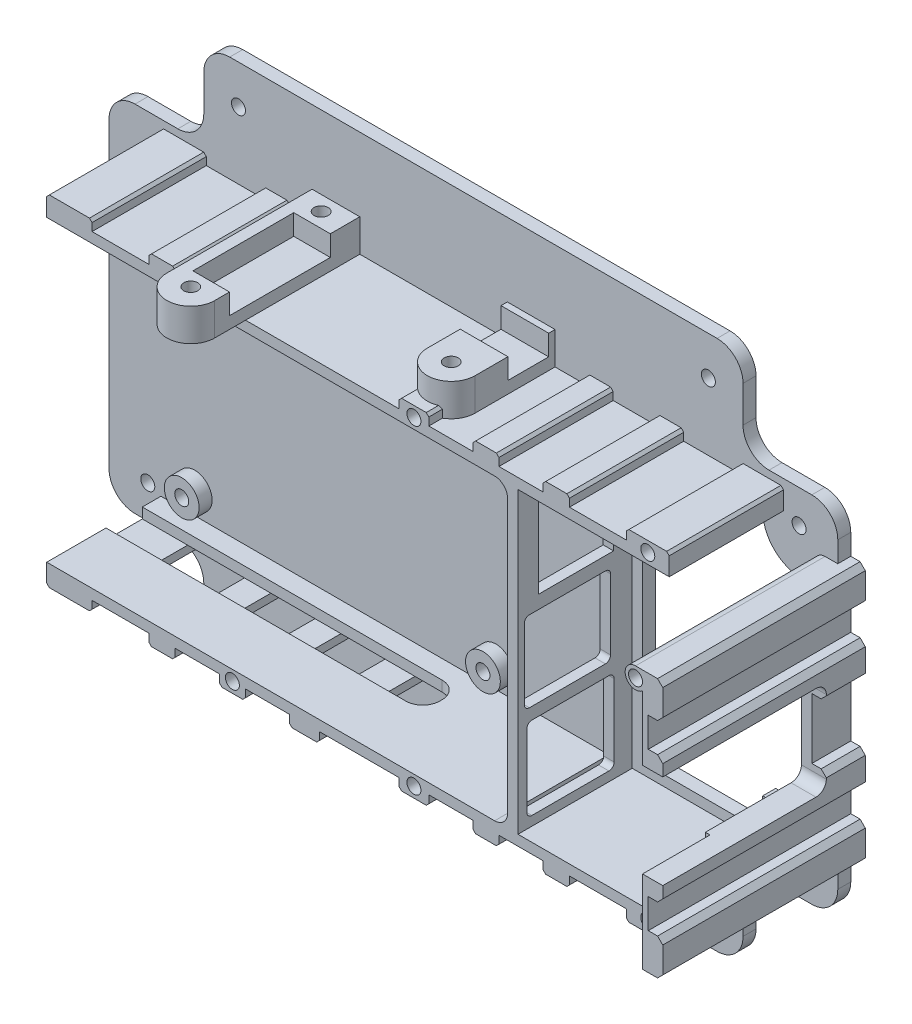
SolidWorks part; units mm, degrees
ref_plane "Front Plane" through (0, 0, 0) normal (0, 0, 1) x (1, 0, 0)
ref_plane "Top Plane" through (0, 0, 0) normal (0, 1, 0) x (1, 0, 0)
ref_plane "Right Plane" through (0, 0, 0) normal (1, 0, 0) x (0, 0, -1)
sketch "Sketch1" plane through (0, 0, 0) normal (0, 0, 1) x (1, 0, 0)
  line L0 (-70.167, -29.1473) -> (-70.167, 29.1473)
  line L1 (-65.167, 34.1473) -> (-56.9198, 34.1473)
  line L2 (-51.9198, 39.1473) -> (-51.9198, 46.117)
  line L3 (-46.9198, 51.117) -> (46.9198, 51.117)
  line L4 (51.9198, 46.117) -> (51.9198, 39.1473)
  line L5 (56.9198, 34.1473) -> (65.167, 34.1473)
  line L6 (70.167, 29.1473) -> (70.167, -29.1473)
  line L7 (65.167, -34.1473) -> (56.9198, -34.1473)
  line L8 (51.9198, -39.1473) -> (51.9198, -46.117)
  line L9 (46.9198, -51.117) -> (-46.9198, -51.117)
  line L10 (-51.9198, -46.117) -> (-51.9198, -39.1473)
  line L11 (-56.9198, -34.1473) -> (-65.167, -34.1473)
  line L12 (44.45, 53.117) -> (-44.45, 53.117) construction
  line L13 (-53.9198, 51.6209) -> (-53.9198, 45.3238) construction
  line L14 (-63.0963, 36.1473) -> (-70.6694, 36.1473) construction
  line L15 (-72.167, 28.575) -> (-72.167, -28.575) construction
  line L16 (-70.6694, -36.1473) -> (-63.0963, -36.1473) construction
  line L18 (-44.45, -53.117) -> (44.45, -53.117) construction
  line L19 (53.9198, 45.3238) -> (53.9198, 51.6209) construction
  line L21 (72.167, -28.575) -> (72.167, 28.575) construction
  circle A1 centre (-62.7062, -27.7812) radius 1.35
  circle A3 centre (-45.2437, -43.6562) radius 1.35
  circle A4 centre (45.2438, -43.6562) radius 1.35
  circle A5 centre (62.7063, -27.7812) radius 1.35
  circle A6 centre (62.7063, 27.7812) radius 1.35
  circle A7 centre (45.2438, 43.6562) radius 1.35
  circle A8 centre (-45.2437, 43.6562) radius 1.35
  circle A9 centre (-62.7062, 27.7812) radius 1.35
  arc A11 (-51.9198, 46.117) -> (-46.9198, 51.117) centre (-46.9198, 46.117) cw
  arc A12 (46.9198, 51.117) -> (51.9198, 46.117) centre (46.9198, 46.117) cw
  arc A13 (65.167, 34.1473) -> (70.167, 29.1473) centre (65.167, 29.1473) cw
  arc A14 (70.167, -29.1473) -> (65.167, -34.1473) centre (65.167, -29.1473) cw
  arc A15 (-46.9198, -51.117) -> (-51.9198, -46.117) centre (-46.9198, -46.117) cw
  arc A16 (46.9198, -51.117) -> (51.9198, -46.117) centre (46.9198, -46.117) ccw
  arc A17 (-65.167, 34.1473) -> (-70.167, 29.1473) centre (-65.167, 29.1473) ccw
  arc A18 (-70.167, -29.1473) -> (-65.167, -34.1473) centre (-65.167, -29.1473) ccw
  arc A19 (-56.9198, -34.1473) -> (-51.9198, -39.1473) centre (-56.9198, -39.1473) cw
  arc A20 (51.9198, -39.1473) -> (56.9198, -34.1473) centre (56.9198, -39.1473) cw
  arc A21 (51.9198, 39.1473) -> (56.9198, 34.1473) centre (56.9198, 39.1473) ccw
  arc A22 (-51.9198, 39.1473) -> (-56.9198, 34.1473) centre (-56.9198, 39.1473) cw
  point P49 (53.9198, 48.4724)
  dimension "D1" = 2.7
  dimension "D10" = 5
  dimension "D11" = 2.7
  dimension "D12" = 2.7
  dimension "D13" = 2.7
  dimension "D14" = 2.7
  dimension "D15" = 2.7
  dimension "D16" = 2.7
  dimension "D17" = 2.7
  dimension "D2" = 2
  dimension "D3" = 2
  dimension "D4" = 2
  dimension "D5" = 2
  dimension "D6" = 2
  dimension "D7" = 2
  dimension "D8" = 2
  dimension "D9" = 2
extrude "Boss-Extrude1" add sketch "Sketch1" along normal blind 2.5
sketch "Sketch3" plane through (0, 0, 2.5) normal (0, 0, 1) x (1, 0, 0)
  line L0 (-53.667, 24.5) -> (-53.667, 34.1473) construction
  line L1 (-70.167, 29.1473) -> (-70.167, -29.1473) construction
  line L2 (-56.9198, 34.1473) -> (-65.167, 34.1473) construction
  line L3 (-53.667, -24.5) -> (-53.667, -34.1473) construction
  line L4 (-65.167, -34.1473) -> (-56.9198, -34.1473) construction
  circle A0 centre (4.333, -24.5) radius 1.35
  circle A1 centre (4.333, 24.5) radius 1.35
  circle A2 centre (-53.667, 24.5) radius 1.35
  circle A3 centre (-53.667, -24.5) radius 1.35
  circle A4 centre (-53.667, 24.5) radius 3.35
  circle A5 centre (-53.667, -24.5) radius 3.35
  circle A6 centre (4.333, -24.5) radius 3.35
  circle A7 centre (4.333, 24.5) radius 3.35
  dimension "D4" = 2.7
  dimension "D5" = 16.5
  dimension "D1" = 49
  dimension "D2" = 58
  dimension "D3" = 2
extrude "Boss-Extrude3" add sketch "Sketch3" along normal blind 2.5
sketch "Sketch4" plane through (0, 0, 2.5) normal (0, 0, 1) x (1, 0, 0)
  circle A0 centre (-53.667, 24.5) radius 1.35
  circle A1 centre (4.333, 24.5) radius 1.35
  circle A2 centre (-53.667, -24.5) radius 1.35
  circle A3 centre (4.333, -24.5) radius 1.35
extrude "Cut-Extrude1" cut sketch "Sketch4" against normal up to surface (2.5 mm away) up to face at (-43.8937, 43.6562, 0)
sketch "Sketch5" plane through (0, 0, 2.5) normal (0, 0, 1) x (1, 0, 0)
  line L0 (24.833, 28) -> (-54.167, 28) construction
  line L1 (-60.167, 28.75) -> (26.083, 28.75)
  line L3 (-60.167, -28.75) -> (26.083, -28.75)
  line L4 (28.583, 26.25) -> (28.583, -26.25)
  line L5 (27.833, -25) -> (27.833, 25) construction
  line L7 (-54.167, -28) -> (24.833, -28) construction
  line L12 (-60.167, 30.75) -> (28.083, 30.75)
  line L14 (-60.167, -30.75) -> (28.083, -30.75)
  line L17 (30.583, 30.75) -> (30.583, -30.75) construction
  line L18 (-62.167, 30.75) -> (-62.167, -30.75) construction
  line L19 (-60.167, 28.75) -> (-60.167, -28.75) construction
  line L20 (-62.167, -30.75) -> (30.583, -30.75) construction
  line L21 (-60.167, -28.75) -> (28.583, -28.75) construction
  line L22 (28.583, 28.75) -> (28.583, -28.75) construction
  line L23 (-62.167, 30.75) -> (30.583, 30.75) construction
  line L24 (-60.167, 28.75) -> (28.583, 28.75) construction
  line L25 (30.583, -28.75) -> (57.7063, -28.75)
  line L27 (59.7063, -30.75) -> (28.083, -30.75)
  line L28 (28.083, 30.75) -> (59.7063, 30.75)
  line L29 (59.7063, 30.75) -> (59.7063, 28.75)
  line L30 (59.7063, 28.75) -> (30.583, 28.75)
  line L31 (-60.167, -28.75) -> (-60.167, -30.75)
  line L32 (-60.167, 28.75) -> (-60.167, 30.75)
  line L33 (30.583, 28.75) -> (30.583, -28.75)
  line L34 (-70.167, 29.1473) -> (-70.167, -29.1473) construction
  line L35 (59.7063, -24.7812) -> (59.7063, -30.75)
  line L36 (59.7063, -25.7) -> (59.7063, 20.73) construction
  line L37 (57.7063, -28.75) -> (57.7063, -22.7813)
  line L38 (67.717, 21.5375) -> (67.717, -23.3459) construction
  line L40 (68.167, 21.2013) -> (68.167, -22.7813)
  line L41 (67.717, 12.679) -> (68.167, 12.679) construction
  line L42 (67.717, 12.679) -> (68.167, 12.679) construction
  line L43 (57.7063, -22.7813) -> (68.167, -22.7813)
  line L45 (59.7063, -24.7812) -> (70.167, -24.7813)
  line L46 (70.167, -29.1473) -> (70.167, 29.1473) construction
  line L47 (70.167, -24.7813) -> (70.167, 25.15)
  line L48 (70.167, 25.15) -> (67.717, 25.15)
  arc A1 (26.083, -28.75) -> (28.583, -26.25) centre (26.083, -26.25) ccw
  arc A3 (26.083, 28.75) -> (28.583, 26.25) centre (26.083, 26.25) cw
  circle A4 centre (62.7063, 27.7812) radius 1.35 construction
  arc A5 (67.717, 25.15) -> (68.167, 21.2013) centre (67.717, 23.15) ccw
  dimension "D5" = 10
  dimension "D7" = 2
  dimension "D1" = 2
  dimension "D2" = 0.75
  dimension "D3" = 0.75
  dimension "D4" = 0.75
  dimension "D6" = 3
  dimension "D8" = 2
extrude "Boss-Extrude4" add sketch "Sketch5" along normal blind 22
sketch "Sketch6" plane through (30.583, 0, 0) normal (1, 0, 0) x (0, 0, -1)
  line L0 (-15.99, -26.45) -> (-13.59, -26.45) construction
  line L1 (-6.99, -11.05) -> (-21.81, -11.05)
  line L2 (-5.99, -12.05) -> (-5.99, -25.95)
  line L3 (-6.99, -26.95) -> (-21.81, -26.95)
  line L4 (-22.81, -12.05) -> (-22.81, -25.95)
  line L5 (-15.99, -11.55) -> (-13.59, -11.55) construction
  line L6 (-6.49, -12.65) -> (-6.49, -13.45) construction
  line L7 (-22.31, -16.25) -> (-22.31, -18.95) construction
  line L8 (-20.93, -8.25) -> (-17.53, -8.25) construction
  line L9 (-22.29, -8.75) -> (-7.67, -8.75)
  line L10 (-23.29, -7.75) -> (-23.29, 5.75)
  line L11 (-22.29, 6.75) -> (-7.67, 6.75)
  line L12 (-6.67, -7.75) -> (-6.67, 5.75)
  line L13 (-20.59, 9.3) -> (-6.09, 9.3)
  line L14 (-20.59, 9.3) -> (-20.59, 26.2)
  line L15 (-20.59, 26.2) -> (-6.09, 26.2)
  line L16 (-6.09, 9.3) -> (-6.09, 26.2)
  line L17 (-7.17, -6.25) -> (-7.17, -1.01) construction
  line L18 (-17.53, 6.25) -> (-20.93, 6.25) construction
  line L19 (-22.79, 4.25) -> (-22.79, -6.25) construction
  line L20 (-6.79, 9.8) -> (-19.89, 9.8) construction
  line L21 (-19.89, 25.7) -> (-6.79, 25.7) construction
  line L22 (-20.09, 10) -> (-20.09, 25.5) construction
  line L23 (-6.59, 20.18) -> (-6.59, 15.12) construction
  arc A0 (-21.81, -11.05) -> (-22.81, -12.05) centre (-21.81, -12.05) ccw
  arc A1 (-21.81, -26.95) -> (-22.81, -25.95) centre (-21.81, -25.95) cw
  arc A2 (-5.99, -25.95) -> (-6.99, -26.95) centre (-6.99, -25.95) cw
  arc A3 (-6.99, -11.05) -> (-5.99, -12.05) centre (-6.99, -12.05) cw
  arc A4 (-7.67, -8.75) -> (-6.67, -7.75) centre (-7.67, -7.75) ccw
  arc A5 (-7.67, 6.75) -> (-6.67, 5.75) centre (-7.67, 5.75) cw
  arc A6 (-23.29, 5.75) -> (-22.29, 6.75) centre (-22.29, 5.75) cw
  arc A7 (-22.29, -8.75) -> (-23.29, -7.75) centre (-22.29, -7.75) cw
  point P10 (-6.49, -13.05)
  point P35 (-19.23, 6.25)
  dimension "D5" = 1
  dimension "D10" = 1
  dimension "D1" = 0.5
  dimension "D2" = 0.5
  dimension "D3" = 0.5
  dimension "D4" = 0.5
  dimension "D6" = 0.5
  dimension "D7" = 0.5
  dimension "D8" = 0.5
  dimension "D9" = 0.5
  dimension "D11" = 0.5
  dimension "D12" = 0.5
  dimension "D13" = 0.5
  dimension "D14" = 0.5
extrude "Cut-Extrude2" cut sketch "Sketch6" against normal up to surface (2 mm away) up to face at (28.583, 0, 13.5)
sketch "Sketch8" plane through (0, -30.75, 0) normal (0, -1, 0) x (1, 0, 0)
  line L0 (-54.167, 6.59) -> (24.833, 6.59) construction
  line L1 (-60.167, 13.09) -> (-2.417, 13.09)
  line L2 (-60.167, 13.09) -> (-60.167, 6.09)
  line L3 (-60.167, 6.09) -> (-2.417, 6.09)
  line L4 (0.833, 9.84) -> (0.833, 9.34)
  line L5 (-3.167, 12.59) -> (-6.667, 12.59) construction
  line L6 (0.333, 6.59) -> (0.333, 12.59) construction
  line L9 (-60.167, 24.5) -> (-60.167, 2.5) construction
  arc A0 (-2.417, 13.09) -> (0.833, 9.84) centre (-2.417, 9.84) cw
  arc A1 (-2.417, 6.09) -> (0.833, 9.34) centre (-2.417, 9.34) ccw
  dimension "D4" = 3.25
  dimension "D1" = 0.5
  dimension "D2" = 0.5
  dimension "D3" = 0.5
extrude "Cut-Extrude3" cut sketch "Sketch8" against normal up to surface (2 mm away) up to face at (-17.042, -28.75, 13.5)
sketch "Sketch9" plane through (0, 0, 2.5) normal (0, 0, 1) x (1, 0, 0)
  line L0 (-60.167, -30.75) -> (59.7063, -30.75) construction
  line L1 (-40.497, -30.75) -> (-35.417, -30.75)
  line L2 (-40.497, -30.75) -> (-40.497, -32.25)
  line L3 (-39.997, -32.75) -> (-35.917, -32.75)
  line L4 (-35.417, -30.75) -> (-35.417, -32.25)
  line L5 (-41.497, -29.5) -> (-41.497, -21.89) construction
  line L6 (-26.917, -30.75) -> (-21.917, -30.75)
  line L7 (-26.917, -30.75) -> (-26.917, -32.25)
  line L8 (-26.417, -32.75) -> (-22.417, -32.75)
  line L9 (-21.917, -30.75) -> (-21.917, -32.25)
  line L10 (-13.417, -30.75) -> (-7.667, -30.75)
  line L11 (-13.417, -30.75) -> (-13.417, -32.25)
  line L12 (-12.917, -32.75) -> (-8.167, -32.75)
  line L13 (-7.667, -30.75) -> (-7.667, -32.25)
  line L14 (-27.917, -29.8) -> (-27.917, -22.3) construction
  line L15 (-20.917, -22.3) -> (-20.917, -29.8) construction
  line L16 (-14.417, -29.8) -> (-14.417, -22.3) construction
  line L17 (-6.667, -15.4) -> (-6.667, -23.8) construction
  line L18 (-34.417, -22.3) -> (-34.417, -29.8) construction
  line L19 (-50.437, -21.89) -> (-50.437, -29.5) construction
  line L20 (-51.437, -30.75) -> (-60.1639, -30.75)
  line L21 (-51.437, -30.75) -> (-51.437, -32.25)
  line L22 (-51.937, -32.75) -> (-59.6639, -32.75)
  line L23 (-60.1639, -30.75) -> (-60.1639, -32.25)
  line L24 (-59.6639, -32.75) -> (-60.1639, -32.25)
  line L25 (-51.437, -32.25) -> (-51.937, -32.75)
  line L26 (-35.917, -32.75) -> (-35.417, -32.25)
  line L27 (-40.497, -32.25) -> (-39.997, -32.75)
  line L28 (-26.917, -32.25) -> (-26.417, -32.75)
  line L29 (-22.417, -32.75) -> (-21.917, -32.25)
  line L30 (-8.167, -32.75) -> (-7.667, -32.25)
  line L31 (-13.417, -32.25) -> (-12.917, -32.75)
  line L32 (-70.167, 0) -> (70.167, 0) construction
  line L33 (-70.167, 29.1473) -> (-70.167, -29.1473) construction
  line L44 (-26.417, 32.75) -> (-22.417, 32.75)
  line L45 (-22.417, 32.75) -> (-21.917, 32.25)
  line L46 (-21.917, 30.75) -> (-21.917, 32.25)
  line L47 (-26.917, 30.75) -> (-21.917, 30.75)
  line L48 (-26.917, 32.25) -> (-26.417, 32.75)
  line L49 (-26.917, 30.75) -> (-26.917, 32.25)
  line L50 (-39.997, 32.75) -> (-35.917, 32.75)
  line L51 (-35.917, 32.75) -> (-35.417, 32.25)
  line L52 (-35.417, 30.75) -> (-35.417, 32.25)
  line L53 (-40.497, 30.75) -> (-35.417, 30.75)
  line L54 (-40.497, 32.25) -> (-39.997, 32.75)
  line L55 (-40.497, 30.75) -> (-40.497, 32.25)
  line L56 (-51.937, 32.75) -> (-59.6639, 32.75)
  line L57 (-59.6639, 32.75) -> (-60.1639, 32.25)
  line L58 (-60.1639, 30.75) -> (-60.1639, 32.25)
  line L59 (-51.437, 30.75) -> (-60.1639, 30.75)
  line L60 (-51.437, 32.25) -> (-51.937, 32.75)
  line L61 (-51.437, 30.75) -> (-51.437, 32.25)
  line L62 (51.437, 32.25) -> (51.937, 32.75)
  line L63 (51.437, 30.75) -> (51.437, 32.25)
  line L64 (51.437, 30.75) -> (59.7063, 30.75)
  line L65 (59.7063, 30.75) -> (59.7063, 32.25)
  line L66 (59.2063, 32.75) -> (59.7063, 32.25)
  line L67 (51.937, 32.75) -> (59.2063, 32.75)
  line L68 (40.497, 32.25) -> (39.997, 32.75)
  line L69 (40.497, 30.75) -> (40.497, 32.25)
  line L70 (40.497, 30.75) -> (35.417, 30.75)
  line L71 (35.417, 30.75) -> (35.417, 32.25)
  line L72 (35.917, 32.75) -> (35.417, 32.25)
  line L73 (39.997, 32.75) -> (35.917, 32.75)
  line L74 (26.917, 32.25) -> (26.417, 32.75)
  line L75 (26.917, 30.75) -> (26.917, 32.25)
  line L76 (26.917, 30.75) -> (21.917, 30.75)
  line L77 (21.917, 30.75) -> (21.917, 32.25)
  line L78 (22.417, 32.75) -> (21.917, 32.25)
  line L79 (26.417, 32.75) -> (22.417, 32.75)
  line L80 (13.417, 32.25) -> (12.917, 32.75)
  line L81 (13.417, 30.75) -> (13.417, 32.25)
  line L82 (13.417, 30.75) -> (7.667, 30.75)
  line L83 (7.667, 30.75) -> (7.667, 32.25)
  line L84 (8.167, 32.75) -> (7.667, 32.25)
  line L85 (12.917, 32.75) -> (8.167, 32.75)
  line L86 (12.917, -32.75) -> (8.167, -32.75)
  line L87 (8.167, -32.75) -> (7.667, -32.25)
  line L88 (7.667, -30.75) -> (7.667, -32.25)
  line L89 (13.417, -30.75) -> (7.667, -30.75)
  line L90 (13.417, -32.25) -> (12.917, -32.75)
  line L91 (13.417, -30.75) -> (13.417, -32.25)
  line L92 (26.417, -32.75) -> (22.417, -32.75)
  line L93 (22.417, -32.75) -> (21.917, -32.25)
  line L94 (21.917, -30.75) -> (21.917, -32.25)
  line L95 (26.917, -30.75) -> (21.917, -30.75)
  line L96 (26.917, -32.25) -> (26.417, -32.75)
  line L97 (26.917, -30.75) -> (26.917, -32.25)
  line L98 (39.997, -32.75) -> (35.917, -32.75)
  line L99 (35.917, -32.75) -> (35.417, -32.25)
  line L100 (35.417, -30.75) -> (35.417, -32.25)
  line L101 (40.497, -30.75) -> (35.417, -30.75)
  line L102 (40.497, -32.25) -> (39.997, -32.75)
  line L103 (40.497, -30.75) -> (40.497, -32.25)
  line L104 (51.937, -32.75) -> (59.2063, -32.75)
  line L105 (59.2063, -32.75) -> (59.7063, -32.25)
  line L106 (59.7063, -30.75) -> (59.7063, -32.25)
  line L107 (51.437, -30.75) -> (59.7063, -30.75)
  line L108 (51.437, -32.25) -> (51.937, -32.75)
  line L109 (51.437, -30.75) -> (51.437, -32.25)
  line L110 (37.957, -32.75) -> (37.957, -30.75) construction
  line L111 (37.957, -30.75) -> (37.957, -28.75) construction
  line L112 (57.7063, -28.75) -> (30.583, -28.75) construction
  line L114 (59.7063, 28.75) -> (59.7063, 30.75) construction
  line L115 (59.7063, -30.75) -> (59.7063, -24.7812) construction
  point P1 (-35.417, -32.75)
  point P2 (-40.497, -32.75)
  point P7 (-21.917, -32.75)
  point P8 (-26.917, -32.75)
  point P11 (-7.667, -32.75)
  point P12 (-13.417, -32.75)
  point P26 (-34.417, -26.05)
  point P28 (-60.1639, -32.75)
  point P29 (-51.437, -32.75)
  dimension "D9" = 135
  dimension "D1" = 1
  dimension "D2" = 1
  dimension "D3" = 1
  dimension "D4" = 1
  dimension "D5" = 1
  dimension "D6" = 1
  dimension "D7" = 1
  dimension "D8" = 2
  dimension "D10" = 135
extrude "Boss-Extrude6" add sketch "Sketch9" along normal up to surface (22 mm away) up to face at (29.8703, -1.1369, 24.5)
sketch "Sketch10" plane through (0, 0, 24.5) normal (0, 0, 1) x (1, 0, 0)
  line L0 (68.167, -22.7813) -> (57.7063, -22.7813) construction
  line L1 (59.7063, -22.7813) -> (68.167, -22.7813)
  line L2 (59.7063, -22.7813) -> (59.7063, -24.7813)
  line L3 (59.7063, -24.7813) -> (70.167, -24.7813)
  line L4 (70.167, -22.7813) -> (70.167, -24.7813)
  line L5 (59.7063, -25.7) -> (59.7063, 20.73) construction
  line L6 (70.167, -24.7813) -> (70.167, 25.15) construction
  line L7 (59.7063, -24.7812) -> (70.167, -24.7813) construction
  line L9 (70.167, 25.15) -> (67.717, 25.15)
  line L10 (70.167, 25.15) -> (70.167, -22.7813)
  line L12 (68.167, 21.2013) -> (68.167, -22.7813)
  arc A0 (67.717, 25.15) -> (68.167, 21.2013) centre (67.717, 23.15) ccw
extrude "Boss-Extrude7" add sketch "Sketch10" along normal blind 1.5
sketch "Sketch11" plane through (0, 0, 26) normal (0, 0, 1) x (1, 0, 0)
  line L0 (59.7063, -24.7813) -> (70.167, -24.7813) construction
  line L2 (70.167, 25.15) -> (70.167, -24.7813)
  line L3 (70.167, -24.7813) -> (69.067, -24.7813)
  line L5 (69.067, 21.6744) -> (69.067, -24.7813)
  line L6 (70.167, 25.15) -> (67.717, 25.15)
  arc A0 (67.717, 25.15) -> (69.067, 21.6744) centre (67.717, 23.15) ccw
  arc A1 (67.717, 25.15) -> (68.167, 21.2013) centre (67.717, 23.15) ccw construction
  dimension "D1" = 1.1
extrude "Boss-Extrude8" add sketch "Sketch11" along normal blind 13
sketch "Sketch12" plane through (0, 0, 39) normal (0, 0, 1) x (1, 0, 0)
  circle A0 centre (67.717, 23.15) radius 1.35
  dimension "D1" = 2.7
extrude "Cut-Extrude4" cut sketch "Sketch12" against normal blind 3 contours A0
sketch "Sketch15" plane through (0, 30.75, 0) normal (0, 1, 0) x (1, 0, 0)
  line L0 (6.5307, -17.9) -> (6.5307, -2.5)
  line L1 (46.9198, -2.5) -> (-46.9198, -2.5) construction
  line L2 (15.7214, -17.9) -> (15.7214, -2.5)
  line L4 (-21.8786, -30.45) -> (-21.8786, -2.5)
  line L5 (-21.8786, -2.5) -> (-31.0693, -2.5)
  line L6 (-31.0693, -2.5) -> (-31.0693, -30.45)
  line L7 (15.7214, -2.5) -> (6.5307, -2.5)
  arc A0 (6.5307, -17.9) -> (15.7214, -17.9) centre (11.1261, -17.9) ccw
  circle A1 centre (11.1261, -17.9) radius 1.35
  circle A3 centre (-26.4739, -5.35) radius 1.35
  arc A4 (-31.0693, -30.45) -> (-21.8786, -30.45) centre (-26.4739, -30.45) ccw
  circle A5 centre (-26.4739, -30.45) radius 1.35
  dimension "D1" = 2.7
  dimension "D2" = 2.7
  dimension "D3" = 2.7
extrude "Boss-Extrude9" add sketch "Sketch15" along normal blind 6.25
sketch "Sketch16" plane through (0, 38.05, 0) normal (0, 1, 0) x (1, 0, 0)
  line L1 (-21.8786, -27.589) -> (-28.9239, -27.589)
  line L2 (-21.8786, -27.589) -> (-21.8786, -8.174)
  line L3 (-21.8786, -8.174) -> (-28.9239, -8.174)
  line L4 (-28.9239, -27.589) -> (-28.9239, -8.174)
  line L6 (-37.5027, -27.089) -> (-26.4452, -27.089) construction
  line L8 (-24.9452, -8.674) -> (-26.4452, -8.674) construction
  line L10 (-21.8786, -30.45) -> (-21.8786, -2.5) construction
  line L11 (-28.9239, -2.9) -> (-28.9239, -32.9) construction
  line L12 (15.7214, -17.9) -> (15.7214, -2.5) construction
  line L13 (15.7214, -11.575) -> (6.5307, -11.575)
  line L14 (15.7214, -11.575) -> (15.7214, -3.725)
  line L15 (15.7214, -3.725) -> (6.5307, -3.725)
  line L16 (6.5307, -11.575) -> (6.5307, -3.725)
  line L17 (6.5307, -2.5) -> (6.5307, -17.9) construction
  line L18 (9.7661, -11.075) -> (13.5761, -11.075) construction
  line L19 (9.7661, -4.725) -> (13.5761, -4.725) construction
  dimension "D1" = 0.5
  dimension "D2" = 0.5
  dimension "D3" = 0.5
  dimension "D4" = 1
extrude "Cut-Extrude5" cut sketch "Sketch16" against normal blind 5
sketch "Sketch17" plane through (0, 0, 24.5) normal (0, 0, 1) x (1, 0, 0)
  line L0 (-26.917, -30.75) -> (-21.917, -30.75) construction
  circle A1 centre (55.5716, -30.75) radius 1.35
  circle A2 centre (10.542, -30.75) radius 1.35
  circle A3 centre (10.5458, 30.75) radius 1.35
  circle A4 centre (55.5754, 30.75) radius 1.35
  circle A5 centre (-24.417, -30.75) radius 1.35
extrude "Cut-Extrude6" cut sketch "Sketch17" against normal blind 3
sketch "Sketch19" plane through (0, 0, 0) normal (0, 0, -1) x (-1, 0, 0)
  line L0 (53.667, -24.5) -> (49.167, -24.5) construction
  line L1 (49.167, -24.5) -> (49.167, -29) construction
  line L3 (-4.333, 24.5) -> (0.167, 24.5) construction
  line L4 (0.167, 24.5) -> (0.167, 29) construction
  circle A0 centre (0.167, -29) radius 1.35
  circle A1 centre (0.167, -29) radius 3.1 construction
  circle A2 centre (0.167, 29) radius 1.35
  circle A3 centre (0.167, 29) radius 3.1 construction
  circle A4 centre (49.167, -29) radius 1.35
  circle A5 centre (49.167, -29) radius 3.1 construction
  circle A6 centre (49.167, 29) radius 1.35
  circle A7 centre (49.167, 29) radius 3.1 construction
  dimension "D1" = 2.7
  dimension "D2" = 1.75
  dimension "D4" = 49
sketch "Sketch20" plane through (0, 0, 39) normal (0, 0, 1) x (1, 0, 0)
  line L0 (72.96, 28.575) -> (72.96, -28.575) construction
  line L1 (70.167, 25.15) -> (71.96, 25.15)
  line L2 (70.167, 25.15) -> (70.167, 18.15)
  line L3 (70.167, 18.15) -> (71.96, 18.15)
  line L4 (72.96, 24.15) -> (72.96, 19.15)
  line L5 (71.96, 25.15) -> (72.96, 24.15)
  line L6 (71.96, 18.15) -> (72.96, 19.15)
  line L7 (70.167, -24.7813) -> (70.167, 25.15) construction
  line L8 (70.167, 12.466) -> (71.96, 12.466)
  line L9 (70.167, 12.466) -> (70.167, 6.0181)
  line L10 (70.167, 6.0181) -> (71.96, 6.0181)
  line L11 (72.96, 11.466) -> (72.96, 7.0181)
  line L12 (71.96, 12.466) -> (72.96, 11.466)
  line L13 (71.96, 6.0181) -> (72.96, 7.0181)
  line L14 (70.167, 0.1844) -> (105.8872, 0.1844) construction
  line L15 (70.167, -12.0972) -> (70.167, -5.6494)
  line L16 (70.167, -12.0972) -> (71.96, -12.0972)
  line L17 (71.96, -12.0972) -> (72.96, -11.0972)
  line L18 (72.96, -11.0972) -> (72.96, -6.6494)
  line L19 (71.96, -5.6494) -> (72.96, -6.6494)
  line L20 (70.167, -5.6494) -> (71.96, -5.6494)
  line L21 (70.167, -24.7813) -> (71.96, -24.7813)
  line L22 (71.96, -24.7813) -> (72.96, -23.7813)
  line L23 (70.167, -24.7813) -> (70.167, -17.7813)
  line L24 (70.167, -17.7813) -> (71.96, -17.7813)
  line L25 (71.96, -17.7813) -> (72.96, -18.7813)
  line L26 (72.96, -23.7813) -> (72.96, -18.7813)
  point P1 (72.96, 18.15)
  point P3 (72.96, 25.15)
  point P12 (72.96, 6.0181)
  point P14 (72.96, 12.466)
  dimension "D1" = 5
extrude "Boss-Extrude11" add sketch "Sketch20" along direction (0, 0, -1) on the side against the normal up to surface (39 mm away) up to face at (2.983, 24.5, 0)
extrude "Cut-Extrude8" cut sketch "Sketch19" against normal offset from surface (2 mm away) 0.5 up to face at (0.983, 24.5, 2.5)
sketch "Sketch21" plane through (0, 0, 2.5) normal (0, 0, 1) x (1, 0, 0)
  line L0 (30.583, -28.75) -> (30.583, 28.75) construction
  line L1 (32.583, 26.75) -> (55.7063, 26.75)
  line L2 (32.583, 26.75) -> (32.583, -26.75)
  line L3 (32.583, -26.75) -> (55.7063, -26.75)
  line L5 (55.7063, -20.7812) -> (66.167, -20.7812)
  line L7 (63.255, 19.2013) -> (66.167, 19.2013)
  line L8 (66.167, -20.7812) -> (66.167, 19.2013)
  line L9 (30.583, 28.75) -> (59.7063, 28.75) construction
  line L11 (68.167, 21.2013) -> (68.167, -22.7813) construction
  line L12 (68.167, -22.7813) -> (59.7063, -22.7813) construction
  line L13 (57.7063, -28.75) -> (30.583, -28.75) construction
  line L14 (55.7063, -20.7812) -> (55.7063, -26.75)
  arc A1 (55.7063, 26.75) -> (63.255, 19.2013) centre (63.255, 26.75) ccw
  dimension "D1" = 2
  dimension "D2" = 2
  dimension "D4" = 2
  dimension "D5" = 2
  dimension "D6" = 2
  dimension "D7" = 2
extrude "Cut-Extrude9" cut sketch "Sketch21" against normal up to surface (2.5 mm away) up to face at (-1.517, 29, 0)
sketch "Sketch22" plane through (0, 0, 39) normal (0, 0, 1) x (1, 0, 0)
  line L0 (72.96, 7.0181) -> (72.96, 11.466) construction
  line L1 (72.96, 9.242) -> (64.4561, 9.242)
  line L2 (72.96, 9.242) -> (72.96, -8.8733)
  line L3 (72.96, -8.8733) -> (64.4561, -8.8733)
  line L4 (64.4561, 9.242) -> (64.4561, -8.8733)
  line L6 (72.96, -11.0972) -> (72.96, -6.6494) construction
  point P10 (72.96, -8.8733)
extrude "Cut-Extrude11" cut sketch "Sketch22" against normal offset from surface (31.5 mm away) 7.5 up to face at (53.2888, -0.5904, 0)
fillet "Fillet1" radius 2 2 edges at (70.5635, -8.8733, 7.5) (70.5635, 9.242, 7.5)
